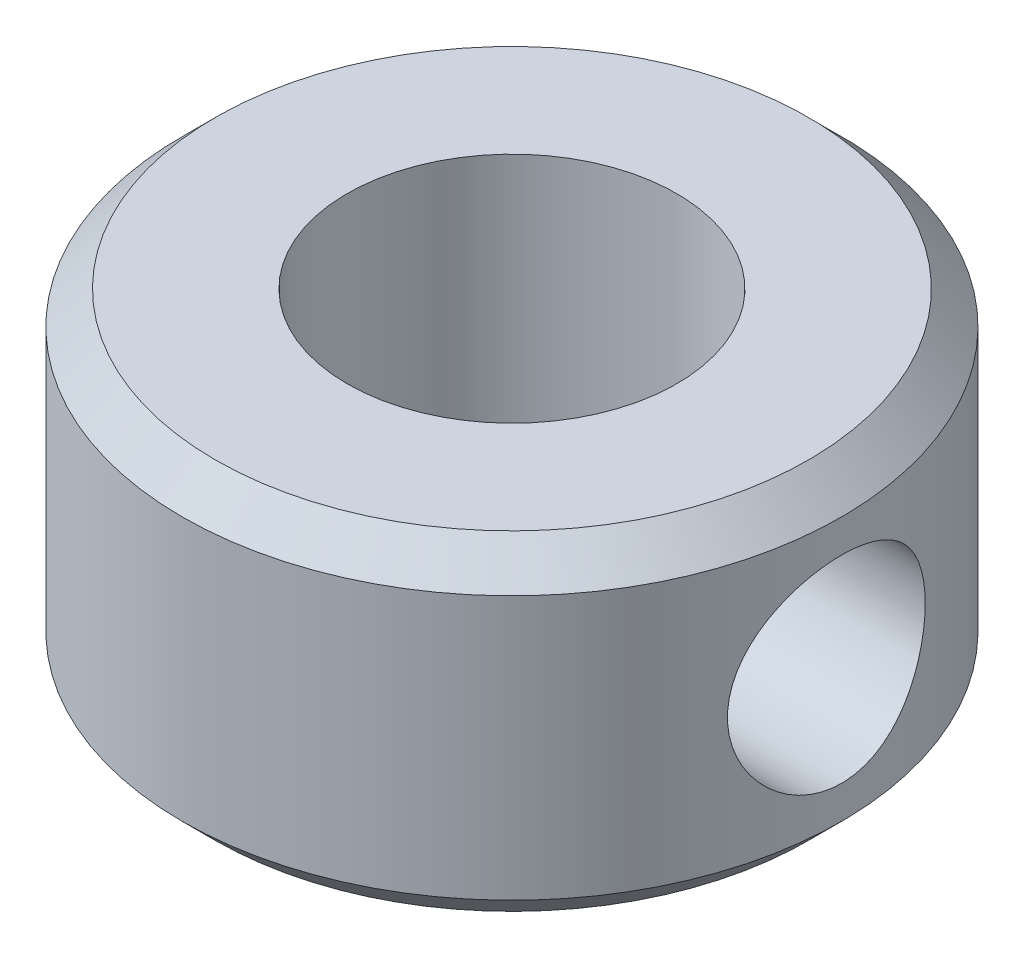
SolidWorks part; units mm, degrees
ref_plane "Front Plane" through (0, 0, 0) normal (0, 0, 1) x (1, 0, 0)
ref_plane "Top Plane" through (0, 0, 0) normal (0, 1, 0) x (1, 0, 0)
ref_plane "Right Plane" through (0, 0, 0) normal (1, 0, 0) x (0, 0, -1)
sketch "Sketch1" plane through (0, 0, 0) normal (0, 1, 0) x (1, 0, 0)
  circle A0 centre (0, 0) radius 2.5
  circle A1 centre (0, 0) radius 5
  dimension "D1" = 5
  dimension "D2" = 10
extrude "Boss-Extrude1" add sketch "Sketch1" along normal blind 5
ref_plane "Plane1" through (5, 0, 0) normal (1, 0, 0) x (0, 0, -1)
sketch "Sketch2" plane through (5, 0, 0) normal (1, 0, 0) x (0, 0, -1)
  line L0 (-5, 2.5) -> (5, 2.5) construction
  line L1 (-5, 5) -> (-5, 0) construction
  line L2 (5, 0) -> (5, 5) construction
  circle A0 centre (0, 2.5) radius 1.5
  dimension "D1" = 3
extrude "Cut-Extrude1" cut sketch "Sketch2" against normal up to surface (3 mm away) up to face at (0, 5, 2.5)
chamfer "Chamfer1" distance 0.5 angle 45 2 edges at (0, 0, 5) (0, 5, 5)
